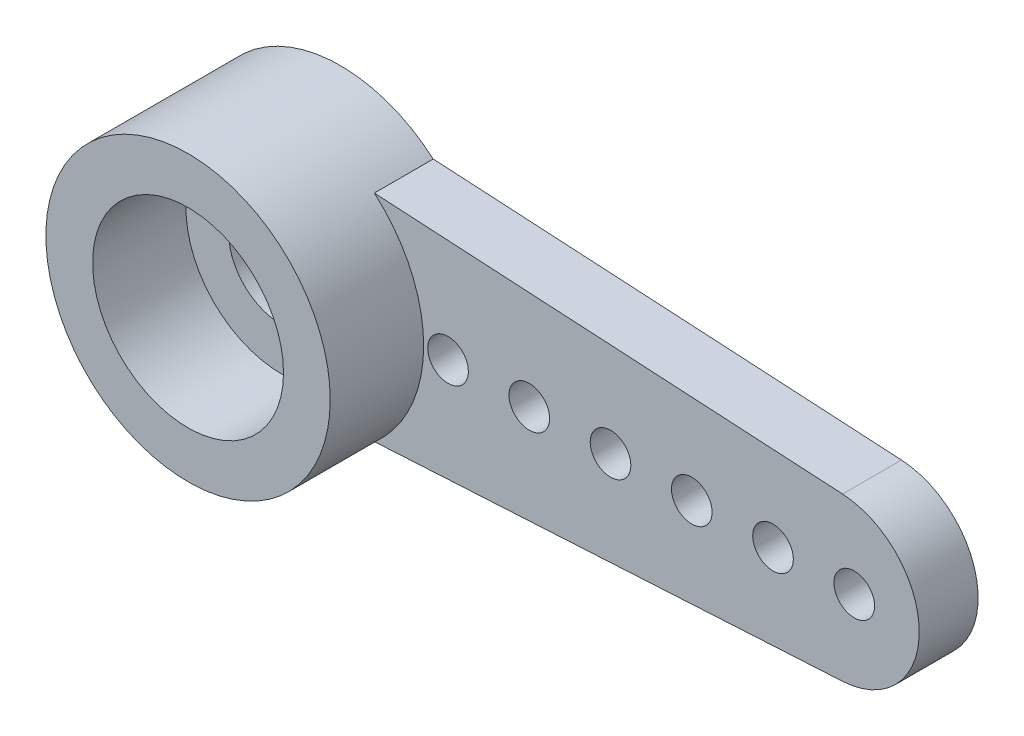
SolidWorks part; units mm, degrees
ref_plane "前视基准面" through (0, 0, 0) normal (0, 0, 1) x (1, 0, 0)
ref_plane "上视基准面" through (0, 0, 0) normal (0, 1, 0) x (1, 0, 0)
ref_plane "右视基准面" through (0, 0, 0) normal (1, 0, 0) x (0, 0, -1)
other "Configuration Table"
sketch "草图1" plane through (0, 0, 0) normal (0, 0, 1) x (1, 0, 0)
  line L0 (-4.9058, 3.0576) -> (16.7875, 1.8282)
  line L1 (-3.5, 8.2939) -> (-3.5, -8.5966) construction
  line L2 (16.004, -1.8726) -> (-5.7967, -3.1081)
  line L3 (15.7, 7.2301) -> (15.7, -7.2734) construction
  line L4 (2.2864, 6.2453) -> (2.2864, -4.4515) construction
  circle A0 centre (13.7, 0) radius 2
  circle A1 centre (0, 0) radius 2.7751
  circle A2 centre (0, 0) radius 3.5
  point P14 (2.2864, -2.65)
  point P15 (2.2864, 2.65)
  point P16 (0, 0)
  dimension "D2" = 7
  dimension "D3" = 4
  dimension "D1" = 19.2
  dimension "D4" = 5.3
extrude "凸台-拉伸1" add sketch "草图1" along normal blind 1.45 contours L2 A2 L0 A1 | A1 | L0 A2 L2 A1 | L0 A2 | L2 A2 | A2 L2 A0 L0 | A0 A2 region at (0.1736, 3.0629, 0) region at (-0.9115, 2.7627, 0) region at (1.218, 2.6457, 0) region at (0, 0, 0) region at (7.4904, 0, 0) region at (0.1736, -3.0629, 0) region at (13.7, 0, 0)
sketch "草图2" plane through (0, 0, 1.45) normal (0, 0, 1) x (1, 0, 0)
  circle A1 centre (0, 0) radius 2.35
  circle A2 centre (0, 0) radius 3.5
  arc A3 (2.2864, 2.65) -> (2.2864, -2.65) centre (0, 0) ccw construction
  dimension "D1" = 4.7
extrude "凸台-拉伸2" add sketch "草图2" along normal blind 2.3
sketch "草图3" plane through (0, 0, 0) normal (0, 0, -1) x (-1, 0, 0)
  circle A0 centre (0, 0) radius 2.3
  dimension "D1" = 4.6
extrude "切除-拉伸1" cut sketch "草图3" against normal blind 0.7
sketch "草图4" plane through (0, 0, 0.7) normal (0, 0, -1) x (-1, 0, 0)
  circle A0 centre (0, 0) radius 1.3
  dimension "D1" = 2.6
extrude "切除-拉伸2" cut sketch "草图4" against normal through all
sketch "草图5" plane through (0, 0, 0) normal (0, 0, -1) x (-1, 0, 0)
  line L0 (-15.7, 4.7285) -> (-15.7, -4.2754) construction
  line L1 (-14.6, 4.1484) -> (-14.6, -4.5312) construction
  arc A1 (-13.8132, 1.9968) -> (-13.8132, -1.9968) centre (-13.7, 0) ccw construction
  circle A2 centre (-14.1, 0) radius 0.5
  dimension "D1" = 1
  dimension "D2" = 1.1
extrude "切除-拉伸3" cut sketch "草图5" against normal through all contours A2
pattern_linear "阵列(线性)1" count 6 spacing 2 along (-1, 0, 0) of "切除-拉伸3"
